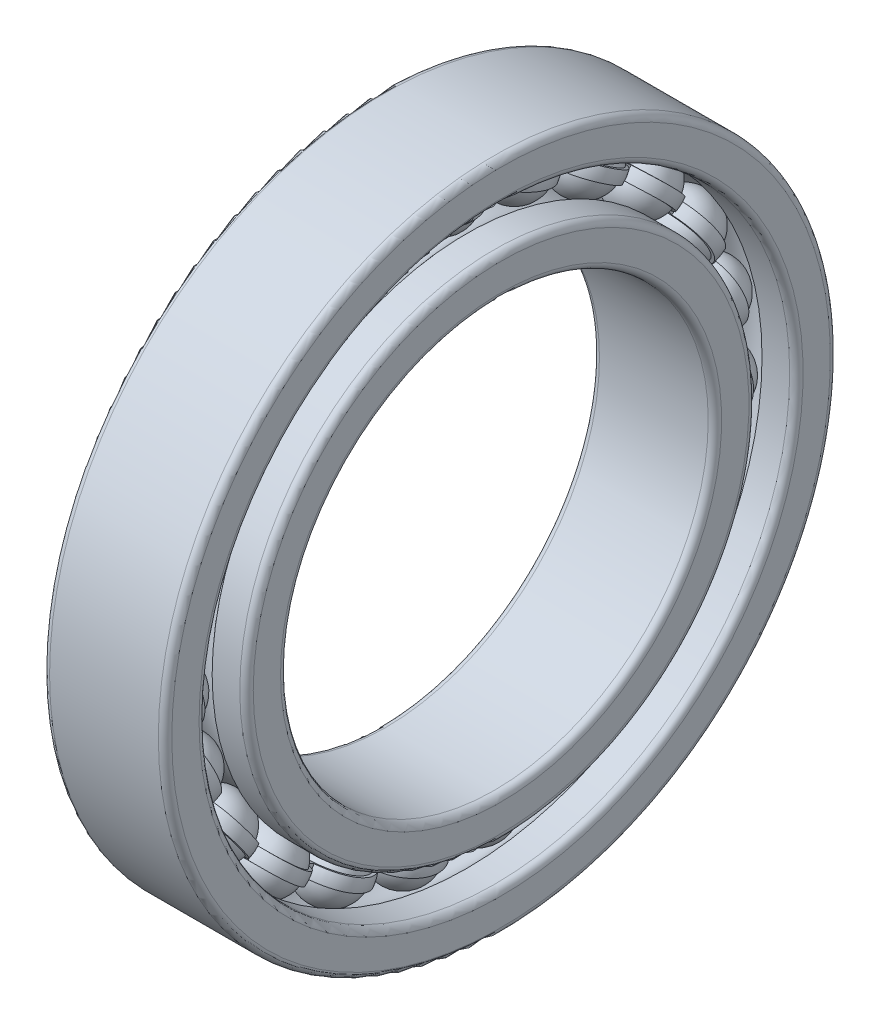
SolidWorks part; units mm, degrees
material "AISI 304"
ref_plane "前视基准面" through (0, 0, 0) normal (0, 0, 1) x (1, 0, 0)
ref_plane "上视基准面" through (0, 0, 0) normal (0, 1, 0) x (1, 0, 0)
ref_plane "右视基准面" through (0, 0, 0) normal (1, 0, 0) x (0, 0, -1)
sketch "尺寸草图" plane through (0, 0, 0) normal (0, 0, 1) x (1, 0, 0)
  line L0 (-19.9271, 0) -> (19.9271, 0) construction
  line L1 (0, 21.603) -> (0, -21.603) construction
  line L2 (-8.9, 55) -> (8.9, 55)
  line L3 (10, 53.9) -> (10, 49.4333)
  line L4 (-10, 53.9) -> (-10, 49.4333)
  line L5 (-8.9, 48.3333) -> (8.9, 48.3333)
  line L6 (-3.5, 45) -> (3.3577, 45) construction
  line L7 (-8.9, 41.6667) -> (8.9, 41.6667)
  line L8 (10, 40.5667) -> (10, 36.1)
  line L9 (8.9, 35) -> (-8.9, 35)
  line L10 (-10, 36.1) -> (-10, 40.5667)
  line L11 (0, 45) -> (0, 50) construction
  circle A0 centre (0, 45) radius 5
  arc A1 (10, 49.4333) -> (8.9, 48.3333) centre (8.9, 49.4333) cw
  arc A2 (10, 40.5667) -> (8.9, 41.6667) centre (8.9, 40.5667) ccw
  arc A3 (-8.9, 41.6667) -> (-10, 40.5667) centre (-8.9, 40.5667) ccw
  arc A4 (-8.9, 48.3333) -> (-10, 49.4333) centre (-8.9, 49.4333) cw
  arc A5 (-8.9, 35) -> (-10, 36.1) centre (-8.9, 36.1) cw
  arc A6 (8.9, 35) -> (10, 36.1) centre (8.9, 36.1) ccw
  arc A7 (10, 53.9) -> (8.9, 55) centre (8.9, 53.9) ccw
  arc A8 (-8.9, 55) -> (-10, 53.9) centre (-8.9, 53.9) ccw
  point P7 (0, 0)
  point P25 (-10, 41.6667)
  point P28 (-10, 48.3333)
  point P31 (-10, 35)
  point P36 (10, 55)
  point P39 (-10, 55)
  dimension "D1" = 1.6667
  dimension "D3" = 1.1
  dimension "B" = 20
  dimension "D2" = 10
  dimension "D" = 110
  dimension "(d)" = 70
  dimension "D5" = 45
  dimension "D6" = 6.6667
  dimension "D7" = 6.6667
sketch "草图2" plane through (0, 0, 0) normal (0, 0, 1) x (1, 0, 0)
  line L6 (8.9, 35) -> (-8.9, 35) construction
  line L8 (-10, 53.9) -> (-10, 49.4333) construction
  line L9 (-8.9, 48.3333) -> (8.9, 48.3333) construction
  line L10 (-8.9, 55) -> (8.9, 55) construction
  line L11 (10, 53.9) -> (10, 49.4333) construction
  line L12 (10, 40.5667) -> (10, 36.1) construction
  line L13 (-8.9, 41.6667) -> (8.9, 41.6667) construction
  line L14 (8.9, 35) -> (-8.9, 35)
  line L15 (-10, 36.1) -> (-10, 40.5667) construction
  line L18 (-3.5, 0) -> (3.5, 0) construction
  line L19 (-19.9271, 0) -> (19.9271, 0) construction
  line L20 (-10, 53.9) -> (-10, 49.4333)
  line L21 (-8.9, 48.3333) -> (-3.7268, 48.3333)
  line L22 (-8.9, 55) -> (8.9, 55)
  line L23 (10, 53.9) -> (10, 49.4333)
  line L24 (10, 40.5667) -> (10, 36.1)
  line L25 (-8.9, 41.6667) -> (-3.7268, 41.6667)
  line L26 (-10, 36.1) -> (-10, 40.5667)
  line L27 (3.7268, 48.3333) -> (8.9, 48.3333)
  line L28 (3.7268, 41.6667) -> (8.9, 41.6667)
  circle A0 centre (0, 45) radius 5 construction
  arc A1 (3.7268, 48.3333) -> (-3.7268, 48.3333) centre (0, 45) ccw
  arc A2 (-3.7268, 41.6667) -> (3.7268, 41.6667) centre (0, 45) ccw
  arc A3 (-8.9, 55) -> (-10, 53.9) centre (-8.9, 53.9) ccw construction
  arc A4 (-10, 49.4333) -> (-8.9, 48.3333) centre (-8.9, 49.4333) ccw construction
  arc A5 (10, 53.9) -> (8.9, 55) centre (8.9, 53.9) ccw construction
  arc A6 (8.9, 48.3333) -> (10, 49.4333) centre (8.9, 49.4333) ccw construction
  arc A7 (10, 40.5667) -> (8.9, 41.6667) centre (8.9, 40.5667) ccw construction
  arc A8 (8.9, 35) -> (10, 36.1) centre (8.9, 36.1) ccw construction
  arc A9 (-8.9, 41.6667) -> (-10, 40.5667) centre (-8.9, 40.5667) ccw construction
  arc A10 (-10, 36.1) -> (-8.9, 35) centre (-8.9, 36.1) ccw construction
  arc A11 (-8.9, 55) -> (-10, 53.9) centre (-8.9, 53.9) ccw
  arc A12 (-10, 49.4333) -> (-8.9, 48.3333) centre (-8.9, 49.4333) ccw
  arc A13 (10, 53.9) -> (8.9, 55) centre (8.9, 53.9) ccw
  arc A14 (8.9, 48.3333) -> (10, 49.4333) centre (8.9, 49.4333) ccw
  arc A15 (10, 40.5667) -> (8.9, 41.6667) centre (8.9, 40.5667) ccw
  arc A16 (8.9, 35) -> (10, 36.1) centre (8.9, 36.1) ccw
  arc A17 (-8.9, 41.6667) -> (-10, 40.5667) centre (-8.9, 40.5667) ccw
  arc A18 (-10, 36.1) -> (-8.9, 35) centre (-8.9, 36.1) ccw
revolve "旋转1" add sketch "草图2" angle 360 about L18
sketch "草图5" plane through (0, 0, 0) normal (0, 0, 1) x (1, 0, 0)
  line L1 (-1.5, 44) -> (1.5, 44)
  line L2 (-1.5, 44) -> (-1.5, 46)
  line L3 (-1.5, 46) -> (1.5, 46)
  line L4 (1.5, 44) -> (1.5, 46)
  line L5 (-1.5, 44) -> (1.5, 46) construction
  line L6 (-1.5, 46) -> (1.5, 44) construction
  circle A0 centre (0, 45) radius 5 construction
  circle A1 centre (0, 45) radius 5 construction
  point P0 (0, 45)
  dimension "D1" = 3
  dimension "D2" = 2
revolve "旋转3" add sketch "草图5" angle 360 about L0
ref_axis "基准轴1" through (-3.85, 0, 0) along (1, 0, 0)
sketch "草图3" plane through (0, 0, 0) normal (0, 0, 1) x (1, 0, 0)
  line L1 (-5.5, 45) -> (5.5, 45)
  circle A0 centre (0, 45) radius 5 construction
  circle A1 centre (0, 45) radius 5 construction
  arc A2 (5.5, 45) -> (-5.5, 45) centre (0, 45) ccw
  dimension "D2" = 11
revolve "旋转2" add sketch "草图3" angle 360 about L1 region at (0, 47.3343, 0)
pattern_circular "阵列(圆周)5" count 23 over 360 about axis through (-3.85, 0, 0) along (1, 0, 0) of bodies 103
sketch "草图6" plane through (0, 0, 0) normal (0, 0, 1) x (1, 0, 0)
  line L0 (-5.4083, 46) -> (5.4083, 46)
  line L1 (-3.5, 45) -> (10, 45) construction
  line L3 (-5.4083, 44) -> (5.4083, 44)
  line L4 (10, -53.9) -> (10, 53.9) construction
  arc A0 (-5.4083, 44) -> (5.4083, 44) centre (0, 45) ccw
  circle A1 centre (0, 45) radius 5 construction
  circle A2 centre (0, 45) radius 5 construction
  arc A3 (5.4083, 46) -> (-5.4083, 46) centre (0, 45) ccw
  dimension "D1" = 11
  dimension "D3" = 1
  dimension "D4" = 1
revolve "切除-旋转1" cut sketch "草图6" angle 360 about L0
sketch "草图7" plane through (0, 0, 0) normal (0, 0, 1) x (1, 0, 0)
  line L0 (-5, 45) -> (5, 45)
  line L1 (-10, 0) -> (10, 0) construction
  line L2 (-10, 53.9) -> (-10, -53.9) construction
  line L3 (10, -53.9) -> (10, 53.9) construction
  circle A0 centre (0, 45) radius 5 construction
  arc A1 (5, 45) -> (-5, 45) centre (0, 45) ccw
revolve "旋转4" add sketch "草图7" angle 360 about L0
pattern_circular "阵列(圆周)2" count 23 over 360 about axis through (-3.85, 0, 0) along (1, 0, 0) of "旋转4"
